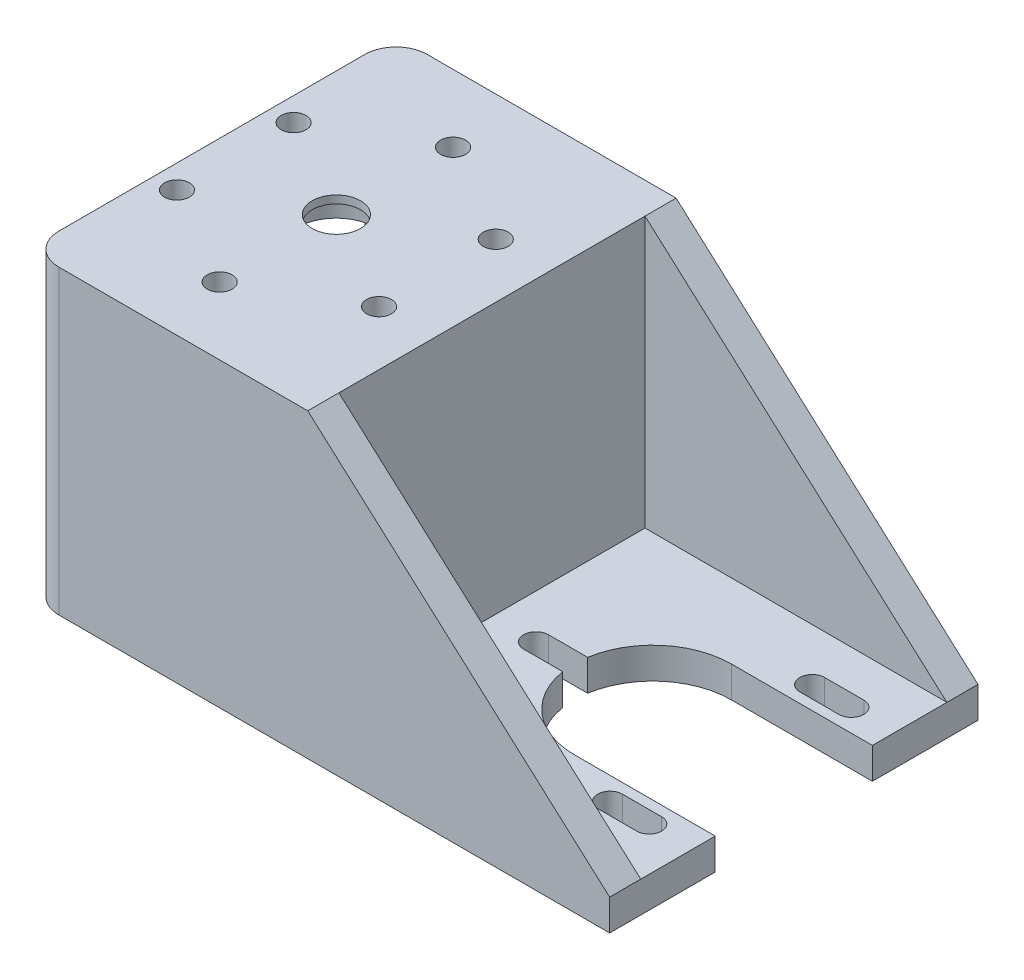
SolidWorks part; units mm, degrees
note: The reader was unsure of these and kept them because the rebuilt part matched: shared geometry of "Sketch3<4>", "Sketch3<5>", "Sketch3<6>".
ref_plane "Front Plane" through (0, 0, 0) normal (0, 0, 1) x (1, 0, 0)
ref_plane "Top Plane" through (0, 0, 0) normal (0, 1, 0) x (1, 0, 0)
ref_plane "Right Plane" through (0, 0, 0) normal (1, 0, 0) x (0, 0, -1)
sketch "Sketch1" plane through (0, 0, 0) normal (0, 0, 1) x (1, 0, 0)
  line L0 (-68.9432, 38.1067) -> (-32.9432, 38.1067)
  line L1 (-32.9432, 38.1067) -> (-32.9432, 3.3767)
  line L2 (-32.9432, 3.3767) -> (8.4068, 3.3767)
  line L3 (8.4068, 3.3767) -> (8.4068, -0.6233)
  line L4 (8.4068, -0.6233) -> (-68.9432, -0.6233)
  line L5 (-68.9432, -0.6233) -> (-68.9432, 3.3767)
  line L6 (-68.9432, 3.3767) -> (-36.9432, 3.3767)
  line L7 (-36.9432, 3.3767) -> (-36.9432, 34.1067)
  line L8 (-36.9432, 34.1067) -> (-68.9432, 34.1067)
  line L9 (-68.9432, 34.1067) -> (-68.9432, 38.1067)
  dimension "D2" = 4
  dimension "D1" = 4
  dimension "D3" = 4
  dimension "D4" = 41.35
  dimension "D5" = 32
  dimension "D6" = 30.73
extrude "Boss-Extrude1" add sketch "Sketch1" along normal blind 39.35
sketch "Sketch3" plane through (0, 3.3767, 0) normal (0, 1, 0) x (1, 0, 0)
  line L0 (-32.9432, -39.35) -> (8.4068, 0)
  line L1 (8.4068, -39.35) -> (8.4068, 0) construction
  line L2 (-36.9432, -39.35) -> (-68.9432, 0)
  line L3 (-12.2682, -19.675) -> (-27.2682, -19.675)
  line L4 (-12.2682, -29.775) -> (8.4068, -29.775)
  line L5 (-12.2682, -29.775) -> (-12.2682, -9.575)
  line L6 (-12.2682, -9.575) -> (8.4068, -9.575)
  line L7 (8.4068, -29.775) -> (8.4068, -9.575)
  line L8 (-60.5917, -20.925) -> (-45.2946, -20.925)
  line L9 (-60.5917, -20.925) -> (-60.5917, -18.425)
  line L10 (-60.5917, -18.425) -> (-45.2946, -18.425)
  line L11 (-45.2946, -20.925) -> (-45.2946, -18.425)
  line L12 (-12.2682, -19.675) -> (-4.7682, -32.6654)
  line L13 (-12.2682, -19.675) -> (-4.7682, -6.6846)
  line L14 (-52.9432, -19.675) -> (-52.9432, -34.675)
  line L15 (-27.2682, -21.275) -> (-22.2406, -21.275)
  line L16 (-27.2682, -21.275) -> (-27.2682, -18.075)
  line L17 (-27.2682, -18.075) -> (-22.2406, -18.075)
  line L18 (-22.2406, -21.275) -> (-22.2406, -18.075)
  line L19 (-4.7682, -34.2654) -> (0.2618, -34.2654)
  line L20 (-4.7682, -34.2654) -> (-4.7682, -31.0654)
  line L21 (-4.7682, -31.0654) -> (0.2618, -31.0654)
  line L22 (0.2618, -34.2654) -> (0.2618, -31.0654)
  line L23 (-4.7682, -5.0846) -> (0.2618, -5.0846)
  line L24 (-4.7682, -5.0846) -> (-4.7682, -8.2846)
  line L25 (-4.7682, -8.2846) -> (0.2618, -8.2846)
  line L26 (0.2618, -5.0846) -> (0.2618, -8.2846)
  line L27 (-52.9432, -19.675) -> (-39.9528, -12.175)
  line L28 (-52.9432, -19.675) -> (-65.9336, -12.175)
  line L29 (-52.9432, -19.675) -> (-52.9432, -4.675)
  line L30 (-52.9432, -19.675) -> (-39.9528, -27.175)
  line L31 (-52.9432, -19.675) -> (-65.9336, -27.175)
  circle A0 centre (-12.2682, -19.675) radius 3.1
  circle A1 centre (-52.9432, -19.675) radius 3.1
  circle A2 centre (-52.9432, -19.675) radius 5.1
  circle A3 centre (-12.2682, -19.675) radius 10.1
  circle A4 centre (-52.9432, -19.675) radius 7.75
  circle A5 centre (-52.9432, -19.675) radius 5.5
  circle A6 centre (-12.2682, -19.675) radius 15
  circle A7 centre (-12.2682, -19.675) radius 14
  circle A8 centre (-4.7682, -32.6654) radius 1.6
  circle A9 centre (-4.7682, -6.6846) radius 1.6
  circle A10 centre (-27.2682, -19.675) radius 1.6
  circle A11 centre (0.2618, -32.6654) radius 1.6
  circle A12 centre (0.2618, -6.6846) radius 1.6
  circle A13 centre (-52.9432, -19.675) radius 15
  circle A14 centre (-52.9432, -34.675) radius 1.6
  circle A15 centre (-65.9336, -27.175) radius 1.6
  circle A16 centre (-65.9336, -12.175) radius 1.6
  circle A17 centre (-52.9432, -4.675) radius 1.6
  circle A18 centre (-39.9528, -12.175) radius 1.6
  circle A19 centre (-39.9528, -27.175) radius 1.6
  point P5 (-12.2682, -29.775)
  point P12 (8.4068, -19.675)
  point P18 (-12.2682, -9.575)
  point P24 (-60.6932, -19.675)
  point P30 (-60.5917, -19.675)
  dimension "D1" = 6.2
  dimension "D2" = 6.2
  dimension "D3" = 10.2
  dimension "D4" = 20.2
  dimension "D6" = 15.5
  dimension "D7" = 11
  dimension "D8" = 28
  dimension "D9" = 30
  dimension "D12" = 3.2
  dimension "D13" = 3.2
  dimension "D14" = 3.2
  dimension "D17" = 30
  dimension "D22" = 3.2
  dimension "D5" = 2.5
  dimension "D10" = 120
  dimension "D11" = 120
  dimension "D15" = 40.675
  dimension "D16" = 5.03
  dimension "D18" = 120
  dimension "D19" = 120
  dimension "D20" = 120
  dimension "D21" = 120
extrude "Cut-Extrude2" cut sketch "Sketch3" against normal blind 3 and the other way offset from surface (33.73 mm away) 3 contours A2 other way up to face at (-52.9432, 34.1067, 19.675)
extrude "Cut-Extrude3" cut sketch "Sketch3<4>" along normal offset from surface (33.73 mm away) 3 contours A5 L8 L11 L10 | A5 L10 L9 L8 up to face at (-58.0432, 34.1067, 19.675) offset beyond the face yes
sketch "Sketch3<4>" plane through (0, 3.3767, 0) normal (0, 1, 0) x (1, 0, 0) same geometry as "Sketch3"
extrude "Cut-Extrude4" cut sketch "Sketch3<5>" against normal through all both and the other way through all contours L4 L7 L6 L5 | A3 | A1 | A8 | L19 L22 L21 L20 | A11 | L23 L26 L25 L24 | A9 | A12 | A10 | L17 L18 L15 L16
sketch "Sketch3<5>" plane through (0, 3.3767, 0) normal (0, 1, 0) x (1, 0, 0) same geometry as "Sketch3"
extrude "Cut-Extrude5" cut sketch "Sketch3<6>" along normal through all contours A14 | A15 | A16 | A17 | A18 | A19
sketch "Sketch3<6>" plane through (0, 3.3767, 0) normal (0, 1, 0) x (1, 0, 0) same geometry as "Sketch3"
sketch "Sketch4" plane through (0, 0, 39.35) normal (0, 0, 1) x (1, 0, 0)
  line L1 (-68.9432, 38.1067) -> (8.4068, 38.1067)
  line L2 (-68.9432, 38.1067) -> (-68.9432, -0.6233)
  line L3 (-68.9432, -0.6233) -> (8.4068, -0.6233)
  line L4 (8.4068, 38.1067) -> (8.4068, -0.6233)
extrude "Boss-Extrude2" add sketch "Sketch4" along normal blind 4
sketch "Sketch5" plane through (0, 0, 0) normal (0, 0, -1) x (-1, 0, 0)
  line L1 (68.9432, 38.1067) -> (-8.4068, 38.1067)
  line L2 (68.9432, 38.1067) -> (68.9432, -0.6233)
  line L3 (68.9432, -0.6233) -> (-8.4068, -0.6233)
  line L4 (-8.4068, 38.1067) -> (-8.4068, -0.6233)
  dimension "D1" = 38.73
extrude "Boss-Extrude3" add sketch "Sketch5" along normal blind 4
sketch "Sketch6" plane through (0, 0, 43.35) normal (0, 0, 1) x (1, 0, 0)
  line L0 (-32.9432, 38.1067) -> (5.8618, 3.3767)
  line L1 (8.4068, 3.3767) -> (-32.9432, 3.3767) construction
  line L2 (5.8618, 3.3767) -> (5.8618, -0.6233)
  line L3 (-68.9432, -0.6233) -> (8.4068, -0.6233) construction
  line L4 (5.8618, -0.6233) -> (8.4068, -0.6233)
  line L5 (8.4068, -0.6233) -> (8.4068, 38.1067)
  line L6 (8.4068, 38.1067) -> (-32.9432, 38.1067)
  line L7 (1.8618, -0.6233) -> (1.8618, 3.3767) construction
  dimension "D1" = 4
extrude "Cut-Extrude6" cut sketch "Sketch6" against normal through all both and the other way through all
fillet "Fillet1" radius 4 2 edges at (-68.9432, 18.7417, -4) (-68.9432, 18.7417, 43.35)
equation "\"h_thickness\"=4"
equation "\"D2@Sketch1\"=\"h_thickness\""
equation "\"v_thickness\"=4"
equation "\"D3@Sketch1\"=\"v_thickness\""
equation "\"enc_od\"=38.35"
equation "\"D4@Sketch1\"=\"enc_od\"+3"
equation "\"shaft_clearance\"=32"
equation "\"D5@Sketch1\"=\"shaft_clearance\""
equation "\"D1@Sketch1\"=\"h_thickness\""
equation "\"tok_height\"=17.2"
equation "\"D6@Sketch1\"=\"tok_height\"+\"pin_collar_height\"-2.8+1"
equation "\"D1@Boss-Extrude1\"=\"enc_od\"+1"
equation "\"shaft_dia\"=6.2"
equation "\"D1@Sketch3\"=\"shaft_dia\""
equation "\"D2@Sketch3\"=\"shaft_dia\""
equation "\"bearing_od\"=10.2"
equation "\"D3@Sketch3\"=\"bearing_od\""
equation "\"enc_collar_dia\"=20.9592"
equation "\"tok_pin_od\"=15.5"
equation "\"D6@Sketch3\"=\"tok_pin_od\""
equation "\"tok_pin_id\"=11"
equation "\"D7@Sketch3\"=\"tok_pin_id\""
equation "\"enc_mounting_28\"=28"
equation "\"D8@Sketch3\"=\"enc_mounting_28\""
equation "\"enc_mount_30\"=30"
equation "\"m3_hole\"=3.2"
equation "\"D14@Sketch3\"=\"m3_hole\""
equation "\"D13@Sketch3\"=\"m3_hole\""
equation "\"D12@Sketch3\"=\"m3_hole\""
equation "\"enc_slide\"=5.03"
equation "\"D16@Sketch3\"=\"enc_slide\""
equation "\"pin_collar_height\"= 15.33"
equation "\"D17@Sketch3\"=\"enc_mount_30\""
equation "\"D9@Sketch3\"=\"enc_mount_30\""
equation "\"D22@Sketch3\"=\"m3_hole\""
equation "\"side_wall_thickness\"=4"
equation "\"D1@Boss-Extrude2\"=\"side_wall_thickness\""
equation "\"D1@Boss-Extrude3\"=\"side_wall_thickness\""
equation "\"D1@Fillet1\"=\"side_wall_thickness\""
